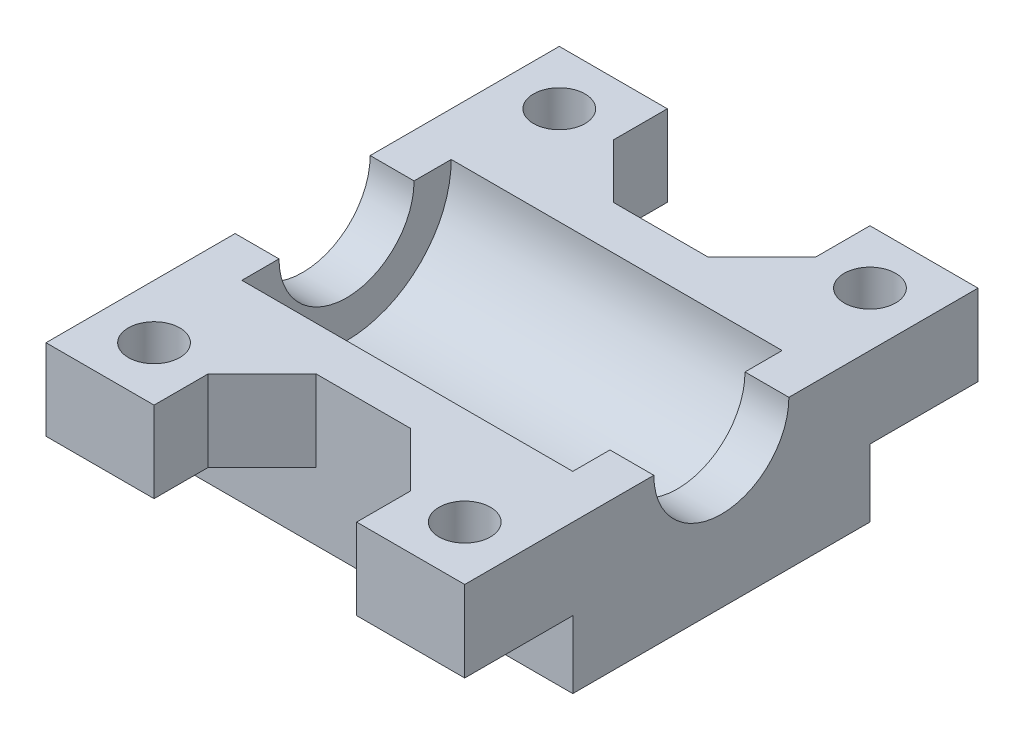
SolidWorks part; units mm, degrees
ref_plane "Front Plane" through (0, 0, 0) normal (0, 0, 1) x (1, 0, 0)
ref_plane "Top Plane" through (0, 0, 0) normal (0, 1, 0) x (1, 0, 0)
ref_plane "Right Plane" through (0, 0, 0) normal (1, 0, 0) x (0, 0, -1)
sketch "Sketch1" plane through (0, 0, 0) normal (0, 1, 0) x (1, 0, 0)
  line L1 (-15.5, 11) -> (15.5, 11)
  line L2 (-15.5, 11) -> (-15.5, -11)
  line L3 (-15.5, -11) -> (15.5, -11)
  line L4 (15.5, 11) -> (15.5, -11)
  line L5 (-15.5, 11) -> (15.5, -11) construction
  line L6 (-15.5, -11) -> (15.5, 11) construction
  point P0 (0, 0)
  dimension "D1" = 31
  dimension "D2" = 22
extrude "Boss-Extrude1" add sketch "Sketch1" along normal blind 11
sketch "Sketch2" plane through (0, 0, 0) normal (0, 1, 0) x (1, 0, 0)
  line L4 (15.5, -11) -> (15.5, 11)
  line L5 (-15.5, -11) -> (15.5, -11)
  line L6 (-15.5, 11) -> (-15.5, -11)
  line L7 (15.5, 11) -> (-15.5, 11)
  line L8 (15.5, -11) -> (15.5, 11)
  line L9 (-15.5, -11) -> (15.5, -11)
  line L10 (-15.5, 11) -> (-15.5, -11)
  line L11 (15.5, 11) -> (-15.5, 11)
  circle A0 centre (0, 0) radius 7.8438
  dimension "D1" = 0
extrude "Boss-Extrude2" [suppressed] add sketch "Sketch2" against normal blind 5
sketch "Sketch3" plane through (0, 11, 0) normal (0, 1, 0) x (1, 0, 0)
  line L1 (12.25, -7.75) -> (-12.25, -7.75)
  line L2 (12.25, -7.75) -> (12.25, 7.75)
  line L3 (12.25, 7.75) -> (-12.25, 7.75)
  line L4 (-12.25, -7.75) -> (-12.25, 7.75)
  line L5 (12.25, -7.75) -> (-12.25, 7.75) construction
  line L6 (12.25, 7.75) -> (-12.25, -7.75) construction
  point P0 (0, 0)
  dimension "D1" = 15.5
  dimension "D2" = 24.5
extrude "Cut-Extrude1" cut sketch "Sketch3" against normal blind 7.75
fillet "Fillet1" radius 7.75 2 edges at (0, 3.25, 7.75) (0, 3.25, -7.75)
sketch "Sketch4" plane through (-12.25, 0, 0) normal (1, 0, 0) x (0, 0, -1)
  line L0 (7.75, 11) -> (-7.75, 11) construction
  circle A0 centre (0, 11) radius 5
  point P4 (0, 0)
  dimension "D1" = 10
extrude "Cut-Extrude2" cut sketch "Sketch4" against normal through all both and the other way through all
sketch "Sketch5" plane through (0, 11, 0) normal (0, 1, 0) x (1, 0, 0)
  line L1 (15.5, -11) -> (7.5, -11)
  line L2 (15.5, -11) -> (15.5, -19)
  line L3 (15.5, -19) -> (7.5, -19)
  line L4 (7.5, -11) -> (7.5, -19)
  circle A0 centre (11.5, -15) radius 1.9058
  dimension "D1" = 8
  dimension "D2" = 8
  dimension "D3" = 4
  dimension "D4" = 4
extrude "Boss-Extrude3" add sketch "Sketch5" against normal blind 6
sketch "Sketch6" plane through (0, 5, 0) normal (0, -1, 0) x (1, 0, 0)
  line L4 (15.5, 11) -> (15.5, 19)
  line L5 (15.5, 19) -> (7.5, 19)
  line L6 (7.5, 19) -> (7.5, 11)
  line L7 (7.5, 11) -> (15.5, 11)
  line L8 (15.5, 11) -> (15.5, 19)
  line L9 (15.5, 19) -> (7.5, 19)
  line L10 (7.5, 19) -> (7.5, 11)
  line L11 (7.5, 11) -> (15.5, 11)
  circle A0 centre (11.5, 15) radius 1.9058 construction
  circle A1 centre (11.5, 15) radius 1.9058
  circle A2 centre (11.5, 15) radius 3
  circle M6 centre (11.5, 15) radius 1.9058
  dimension "D2" = 6
  dimension "D1" = 0
extrude "Cut-Extrude3" [suppressed] cut sketch "Sketch6" against normal blind 3 contours A2 M6
mirror "Mirror8" about plane through (0, 0, 0) normal (1, 0, 0) of "Cut-Extrude3", "Boss-Extrude3"
mirror "Mirror9" about plane through (0, 0, 0) normal (0, 0, 1) of "Mirror8"
chamfer "Chamfer2" [suppressed] distance 4 angle 45
sketch "Sketch7" plane through (0, 5, 0) normal (0, -1, 0) x (1, 0, 0)
  line L1 (14.6754, 15) -> (13.0877, 17.75)
  line L2 (13.0877, 17.75) -> (9.9123, 17.75)
  line L3 (9.9123, 17.75) -> (8.3246, 15)
  line L4 (8.3246, 15) -> (9.9123, 12.25)
  line L5 (9.9123, 12.25) -> (13.0877, 12.25)
  line L6 (13.0877, 12.25) -> (14.6754, 15)
  circle A0 centre (11.5, 15) radius 1.9058 construction
  circle A1 centre (11.5, 15) radius 1.9058
  circle A2 centre (11.5, 15) radius 2.75 construction
  dimension "D1" = 5.5
extrude "Cut-Extrude4" cut sketch "Sketch7" against normal blind 2
mirror "Mirror10" about plane through (0, 0, 0) normal (1, 0, 0) of "Cut-Extrude4"
mirror "Mirror11" about plane through (0, 0, 0) normal (0, 0, 1) of "Mirror10"
chamfer "Chamfer3" distance 4 angle 45 4 edges at (-7.5, 8, 11) (7.5, 8, 11) (7.5, 8, -11) (-7.5, 8, -11)
